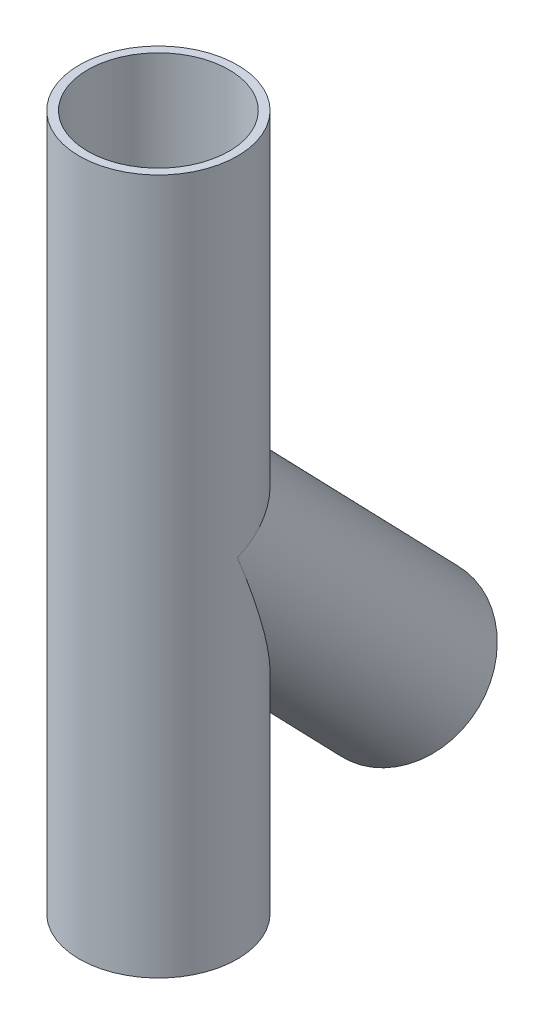
SolidWorks part; units mm, degrees
ref_plane "Alzado" through (0, 0, 0) normal (0, 0, 1) x (1, 0, 0)
ref_plane "Planta" through (0, 0, 0) normal (0, 1, 0) x (1, 0, 0)
ref_plane "Vista lateral" through (0, 0, 0) normal (1, 0, 0) x (0, 0, -1)
sketch "Croquis1" plane through (0, 0, 0) normal (0, 1, 0) x (1, 0, 0)
  circle A0 centre (0, 0) radius 25.4
  circle A1 centre (0, 0) radius 28.4
  dimension "D1" = 50.8
  dimension "D2" = 3
extrude "Saliente-Extruir1" add sketch "Croquis1" along normal blind 125 and the other way blind 125
sketch "Croquis3" plane through (0, 0, 0) normal (1, 0, 0) x (0, 0, -1)
  line L0 (0, 0) -> (122.2384, 118.0442) construction
  line L1 (0, 0) -> (0, 125) construction
  line L2 (25.4, 125) -> (-25.4, 125) construction
  dimension "D1" = 46
ref_plane "Plano2" through (0, 0, 0) normal (0, -0.7193, -0.6947) x (0, 0.6947, -0.7193)
sketch "Croquis4" plane through (0, 0, 0) normal (0, -0.7193, -0.6947) x (0, 0.6947, -0.7193)
  circle A0 centre (0, 0) radius 25.4
  circle A1 centre (0, 0) radius 28.4
  dimension "D1" = 50.8
  dimension "D2" = 3
extrude "Saliente-Extruir3" add sketch "Croquis4" along normal blind 125
